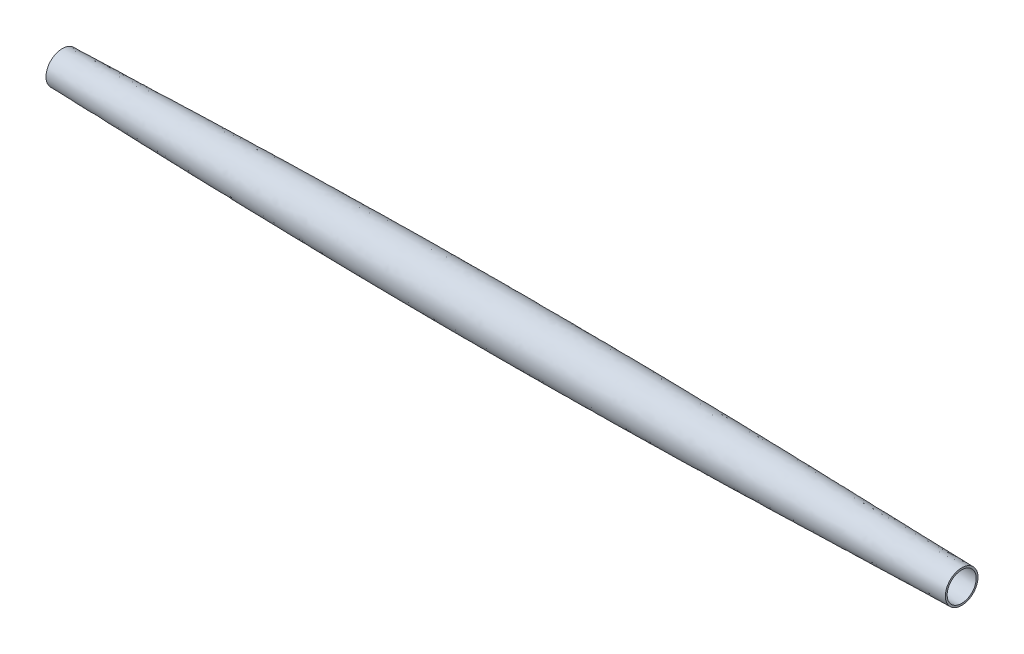
SolidWorks part; units mm, degrees
ref_plane "Front Plane" through (0, 0, 0) normal (0, 0, 1) x (1, 0, 0)
ref_plane "Top Plane" through (0, 0, 0) normal (0, 1, 0) x (1, 0, 0)
ref_plane "Right Plane" through (0, 0, 0) normal (1, 0, 0) x (0, 0, -1)
ref_plane "Plane1" through (-303.53, 0, 0) normal (1, 0, 0) x (0, 0, -1)
ref_plane "Plane2" through (-607.06, 0, 0) normal (1, 0, 0) x (0, 0, -1)
sketch "Sketch1" plane through (0, 0, 0) normal (1, 0, 0) x (0, 0, -1)
  circle A0 centre (0, 0) radius 11.015
  circle A1 centre (0, 0) radius 9.805
  dimension "D1" = 22.03
  dimension "D2" = 1.21
sketch "Sketch3" plane through (-303.53, 0, 0) normal (1, 0, 0) x (0, 0, -1)
  circle A0 centre (0, 0) radius 15.975
  circle A1 centre (0, 0) radius 14.765
  dimension "D1" = 31.95
  dimension "D2" = 1.21
sketch "Sketch4" plane through (-607.06, 0, 0) normal (1, 0, 0) x (0, 0, -1)
  circle A0 centre (0, 0) radius 11.015
  circle A1 centre (0, 0) radius 9.805
  dimension "D1" = 22.03
  dimension "D2" = 1.21
loft "Loft5" add section "Sketch1" section "Sketch3" section "Sketch4" start constraint default end constraint default connector at (0, -9.5714, 5.4515) connector at (-303.53, -15.9692, 0.4316) connector at (-607.06, -10.0133, 4.5895)
loft "Cut-Loft1" cut section "Sketch1<6>" section "Sketch3<6>" section "Sketch4<3>" connector at (0, 2.0908, -9.5795) connector at (-303.53, -2.4105, -14.5669) connector at (-607.06, -2.1028, -9.5769)
sketch "Sketch1<6>" plane through (0, 0, 0) normal (1, 0, 0) x (0, 0, -1) same geometry as "Sketch1"
sketch "Sketch3<6>" plane through (-303.53, 0, 0) normal (1, 0, 0) x (0, 0, -1) same geometry as "Sketch3"
sketch "Sketch4<3>" plane through (-607.06, 0, 0) normal (1, 0, 0) x (0, 0, -1) same geometry as "Sketch4"
